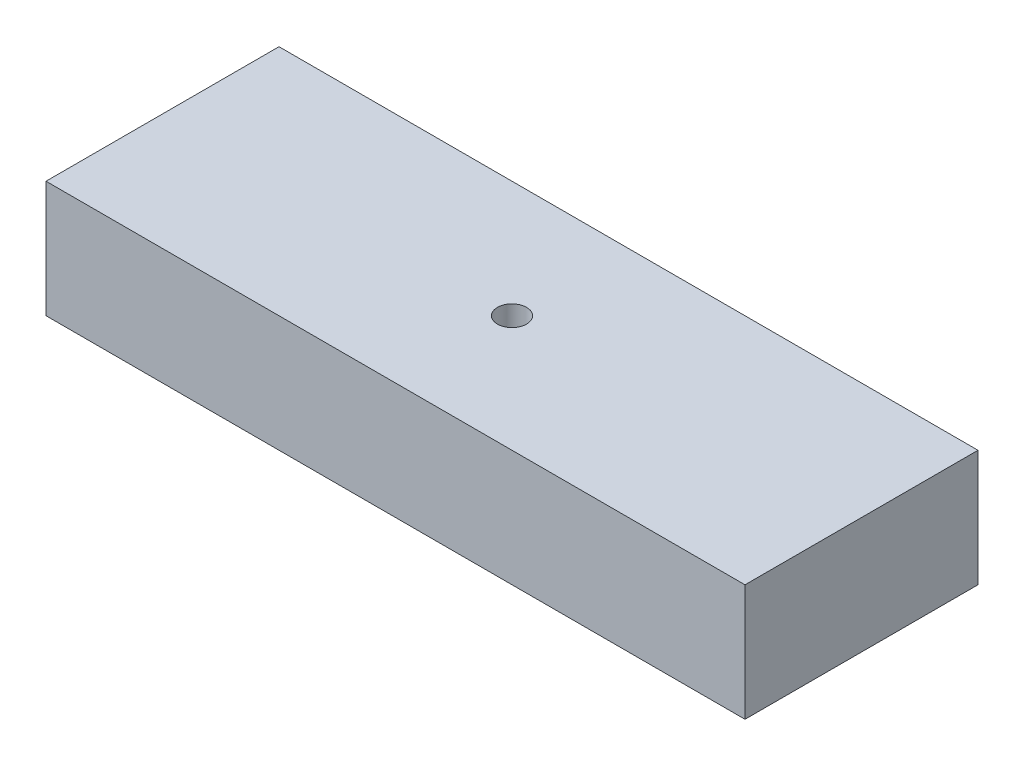
SolidWorks part; units mm, degrees
ref_plane "Front Plane" through (0, 0, 0) normal (0, 0, 1) x (1, 0, 0)
ref_plane "Top Plane" through (0, 0, 0) normal (0, 1, 0) x (1, 0, 0)
ref_plane "Right Plane" through (0, 0, 0) normal (1, 0, 0) x (0, 0, -1)
sketch "Sketch1" plane through (0, 0, 0) normal (0, 1, 0) x (1, 0, 0)
  line L1 (-152.4, -50.8) -> (152.4, -50.8)
  line L2 (-152.4, -50.8) -> (-152.4, 50.8)
  line L3 (-152.4, 50.8) -> (152.4, 50.8)
  line L4 (152.4, -50.8) -> (152.4, 50.8)
  line L5 (-152.4, -50.8) -> (152.4, 50.8) construction
  line L6 (-152.4, 50.8) -> (152.4, -50.8) construction
  point P0 (0, 0)
  dimension "D1" = 101.6
  dimension "D2" = 304.8
extrude "Boss-Extrude1" add sketch "Sketch1" along normal blind 50.8
hole_wizard "1/2 (0.5) Diameter Hole1" positions "Sketch2" profile "Sketch3" hole size "1/2" standard "ANSI Inch" end condition through all
sketch "Sketch2" plane through (0, 50.8, 0) normal (0, 1, 0) x (1, 0, 0)
  point P0 (0, 0)
sketch "Sketch3" plane through (0, 50.8, 0) normal (1, 0, 0) x (0, 0, 1)
  line L0 (0, 0) -> (0, 50.8)
  line L1 (0, 50.8) -> (6.35, 50.8)
  line L2 (6.35, 50.8) -> (6.35, 0)
  line L5 (6.35, 0) -> (0, 0)
  line L11 (0, -6.35) -> (0, 107.95) construction
  dimension "Thru Hole Dia." = 12.7
  dimension "Thru Hole Depth" = 50.8
